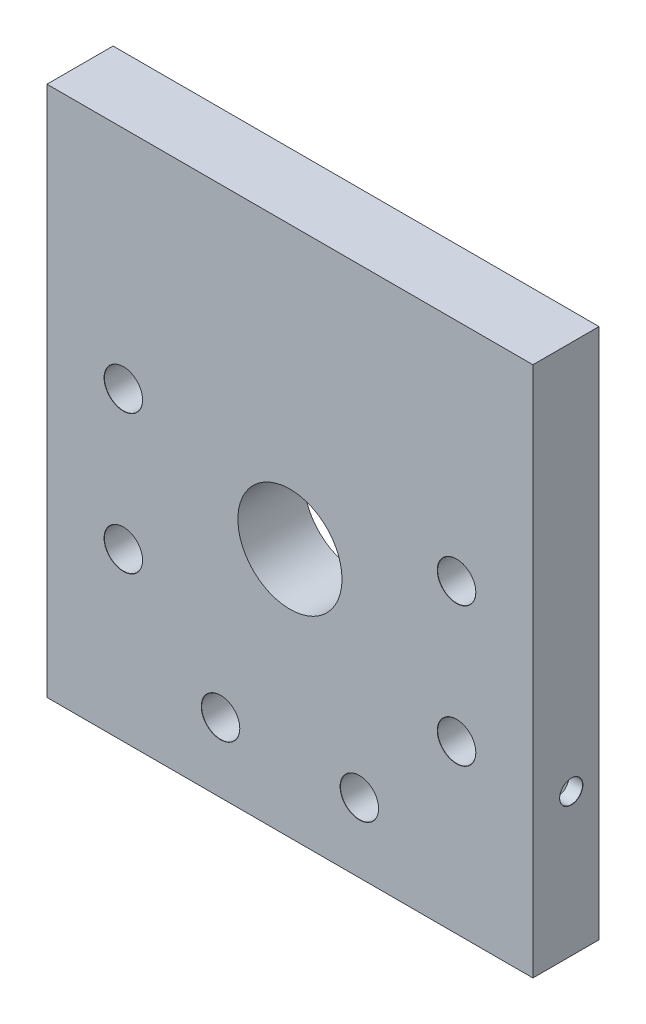
SolidWorks part; units mm, degrees
material "1060 Alloy"
ref_plane "Front Plane" through (0, 0, 0) normal (0, 0, 1) x (1, 0, 0)
ref_plane "Top Plane" through (0, 0, 0) normal (0, 1, 0) x (1, 0, 0)
ref_plane "Right Plane" through (0, 0, 0) normal (1, 0, 0) x (0, 0, -1)
sketch "Sketch1" plane through (0, 0, 0) normal (0, 0, 1) x (1, 0, 0)
  line L1 (-35, -65) -> (35, -65)
  line L2 (-35, -65) -> (-35, 65)
  line L3 (-35, 65) -> (35, 65)
  line L4 (35, -65) -> (35, 65)
  line L5 (-35, -65) -> (35, 65) construction
  line L6 (-35, 65) -> (35, -65) construction
  point P0 (0, 0)
  dimension "D1" = 130
  dimension "D2" = 70
extrude "Boss-Extrude1" add sketch "Sketch1" along normal blind 9.525
sketch "Sketch2" plane through (0, -65, 0) normal (0, -1, 0) x (1, 0, 0)
  line L0 (-35, 4.7625) -> (35, 4.7625) construction
  line L1 (-35, 9.525) -> (-35, 0) construction
  line L2 (35, 9.525) -> (35, 0) construction
  line L3 (0, -55) -> (0, 55) construction
  point P6 (-20, 4.7625)
  point P9 (20, 4.7625)
  dimension "D1" = 15
hole_wizard "Tap Drill for M4x0.7 Tap1" positions "Sketch3" profile "Sketch4" hole size "M4x0.7" standard "ANSI Metric"
sketch "Sketch3" plane through (0, -65, 0) normal (0, -1, 0) x (-1, 0, 0)
  point P0 (20, -4.7625)
  point P3 (-20, -4.7625)
sketch "Sketch4" plane through (-20, -65, 4.7625) normal (1, 0, 0) x (0, 0, -1)
  line L0 (0, 0) -> (0, 2.9914)
  line L1 (0, 2.9914) -> (1.65, 2)
  line L2 (1.65, 2) -> (1.65, 0.025)
  line L3 (1.65, 0.025) -> (1.675, 0)
  line L5 (1.675, 0) -> (0, 0)
  line L6 (-1.65, 0.025) -> (-1.675, 0) construction
  line L10 (0, 2.9914) -> (-1.65, 2) construction
  line L11 (0, -6.35) -> (0, 107.95) construction
  dimension "Hole Dia." = 3.3
  dimension "Hole Depth" = 2
  dimension "Near C'Sink Dia." = 3.35
  dimension "Near C'Sink Angle" = 90
  dimension "Drill Angle" = 118
sketch "Sketch5" plane through (0, 0, 9.525) normal (0, 0, 1) x (1, 0, 0)
  line L0 (0, -5.2388) -> (0, 5.2388) construction
  line L1 (35, 65) -> (-35, 65) construction
  line L3 (35, 65) -> (-35, 65) construction
  point P0 (10, 55)
  point P1 (24, 41)
  point P2 (24, 21)
  point P3 (0, 29)
  point P4 (0, 0)
  point P8 (0, 65)
  point P11 (-24, 21)
  point P12 (-24, 41)
  point P13 (-10, 55)
  dimension "D1" = 26
  dimension "D2" = 10
  dimension "D3" = 20
  dimension "D4" = 8
  dimension "D5" = 24
  dimension "D6" = 10
sketch "Sketch6" plane through (0, 0, 9.525) normal (0, 0, 1) x (1, 0, 0)
  circle A0 centre (0, 29) radius 7.5
  dimension "D1" = 15
extrude "Cut-Extrude1" cut sketch "Sketch6" against normal through all
hole_wizard "M5 Clearance Hole1" positions "Sketch11" profile "Sketch12" hole size "M5" standard "ANSI Metric" end condition through all
sketch "Sketch11" plane through (0, 0, 9.525) normal (0, 0, 1) x (1, 0, 0)
  point P0 (-10, 55)
  point P3 (10, 55)
  point P6 (24, 41)
  point P9 (24, 21)
  point P12 (-24, 41)
  point P15 (-24, 21)
sketch "Sketch12" plane through (-10, 55, 9.525) normal (1, 0, 0) x (0, -1, 0)
  line L0 (0, 0) -> (0, 9.525)
  line L1 (0, 9.525) -> (2.75, 9.525)
  line L2 (2.75, 9.525) -> (2.75, 0.025)
  line L3 (2.75, 0.025) -> (2.775, 0)
  line L5 (2.775, 0) -> (0, 0)
  line L6 (-2.75, 0.025) -> (-2.775, 0) construction
  line L11 (0, -6.35) -> (0, 107.95) construction
  dimension "Thru Hole Dia." = 5.5
  dimension "Thru Hole Depth" = 9.525
  dimension "Near C'Sink Dia." = 5.55
  dimension "Near C'Sink Angle" = 90
sketch "Sketch13" plane through (35, 0, 0) normal (1, 0, 0) x (0, 0, -1)
  line L0 (-4, -35) -> (-4, 35) construction
  line L2 (-9.525, -65) -> (0, -65) construction
  line L4 (0, -65) -> (0, 65) construction
  point P5 (-4, -44.5)
  point P8 (0, 0)
  point P9 (0, 0)
  point P10 (0, 0)
  point P11 (0, 0)
  dimension "D1" = 20.5
  dimension "D2" = 4
hole_wizard "Tap Drill for M4x0.7 Tap2" positions "Sketch14" profile "Sketch16" hole size "M4x0.7" standard "ANSI Metric"
sketch "Sketch14" plane through (35, 0, 0) normal (1, 0, 0) x (0, 0, -1)
  point P0 (-4, -44.5)
sketch "Sketch16" plane through (35, -44.5, 4) normal (0, 1, 0) x (0, 0, -1)
  line L0 (0, 0) -> (0, 2.9914)
  line L1 (0, 2.9914) -> (1.65, 2)
  line L2 (1.65, 2) -> (1.65, 0.025)
  line L3 (1.65, 0.025) -> (1.675, 0)
  line L5 (1.675, 0) -> (0, 0)
  line L6 (-1.65, 0.025) -> (-1.675, 0) construction
  line L10 (0, 2.9914) -> (-1.65, 2) construction
  line L11 (0, -6.35) -> (0, 107.95) construction
  dimension "Hole Dia." = 3.3
  dimension "Hole Depth" = 2
  dimension "Near C'Sink Dia." = 3.35
  dimension "Near C'Sink Angle" = 90
  dimension "Drill Angle" = 118
mirror "Mirror1" about plane through (0, 0, 0) normal (1, 0, 0) of "Tap Drill for M4x0.7 Tap2"
mirror "Mirror3" about plane through (0, 0, 0) normal (0, 1, 0) of "Cut-Extrude1", "M5 Clearance Hole1"
sketch "Sketch17" plane through (0, 0, 9.525) normal (0, 0, 1) x (1, 0, 0)
  line L1 (-58.4494, 77.8341) -> (59.9809, 77.8341)
  line L2 (-58.4494, 77.8341) -> (-58.4494, 11.5056)
  line L3 (-58.4494, 11.5056) -> (59.9809, 11.5056)
  line L4 (59.9809, 77.8341) -> (59.9809, 11.5056)
extrude "Cut-Extrude2" cut sketch "Sketch17" against normal through all
